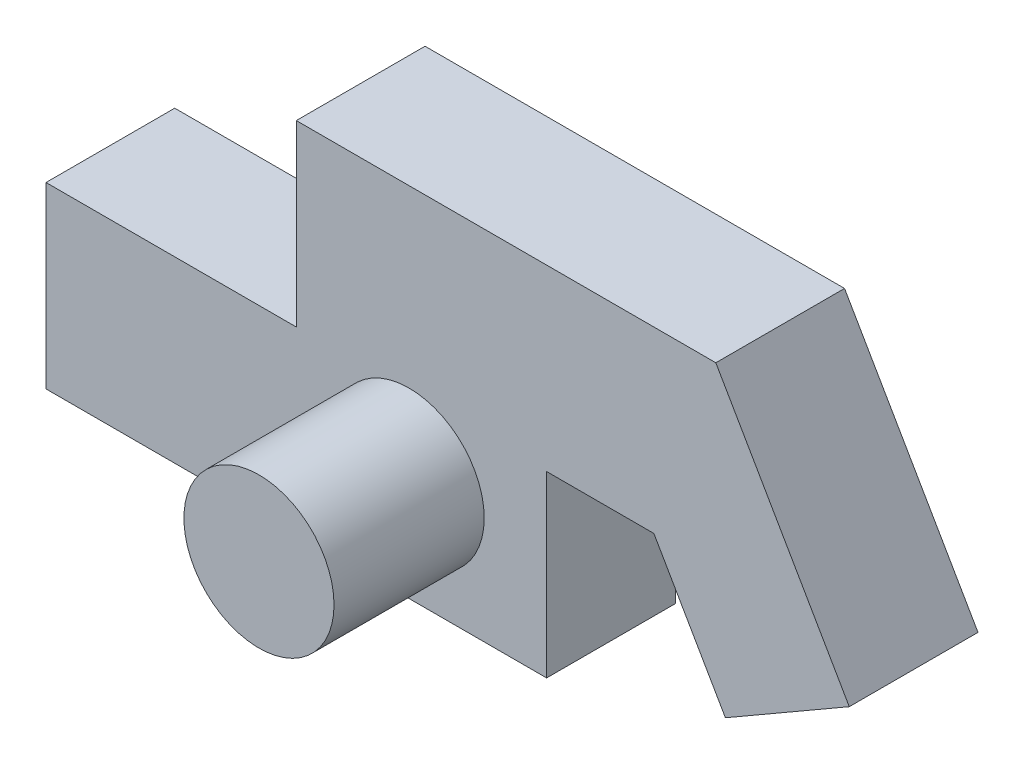
SolidWorks part; units mm, degrees
ref_plane "Plano frontal" through (0, 0, 0) normal (0, 0, 1) x (1, 0, 0)
ref_plane "Plano superior" through (0, 0, 0) normal (0, 1, 0) x (1, 0, 0)
ref_plane "Plano direito" through (0, 0, 0) normal (1, 0, 0) x (0, 0, -1)
sketch "Esboço1" plane through (0, 0, 0) normal (0, 0, 1) x (1, 0, 0)
  line L1 (70, 0) -> (70, 25)
  line L2 (70, 25) -> (85, 25)
  line L3 (85, 25) -> (95, 7.6795)
  line L4 (95, 7.6795) -> (112.3205, 17.6795)
  line L5 (112.3205, 17.6795) -> (93.6603, 50)
  line L6 (93.6603, 50) -> (35, 50)
  line L7 (35, 50) -> (35, 25)
  line L8 (35, 25) -> (0, 25)
  line L9 (0, 25) -> (0, 0)
  line L10 (0, 0) -> (70, 0)
  dimension "D1" = 70
  dimension "D2" = 35
  dimension "D3" = 25
  dimension "D4" = 15
  dimension "D5" = 120
  dimension "D6" = 20
  dimension "D7" = 20
extrude "Ressalto-extrusão1" add sketch "Esboço1" along normal blind 18 contours L10 L1 L2 L3 L4 L5 L6 L7 L8 L9
sketch "Esboço2" plane through (0, 0, 18) normal (0, 0, 1) x (1, 0, 0)
  circle A0 centre (50.7795, 14.9952) radius 10.4956
extrude "Ressalto-extrusão2" add sketch "Esboço2" along normal blind 21
